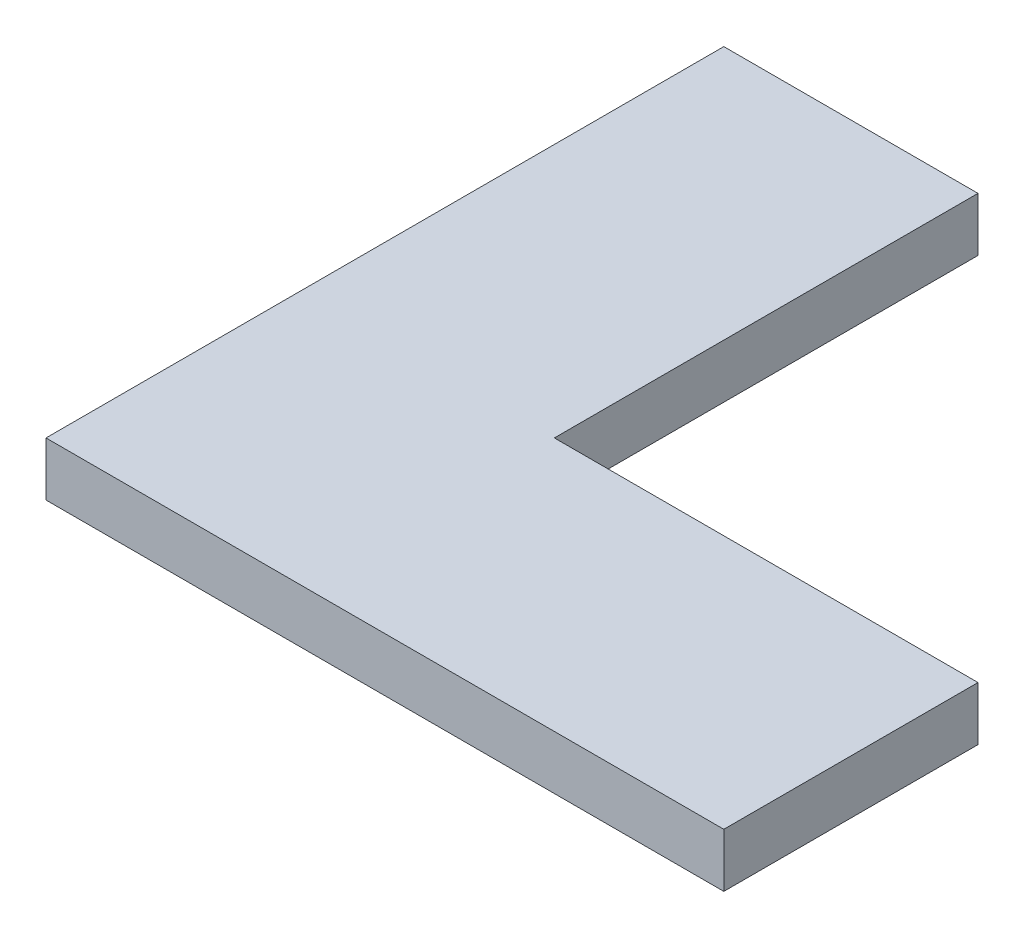
SolidWorks part; units mm, degrees
ref_plane "Front Plane" through (0, 0, 0) normal (0, 0, 1) x (1, 0, 0)
ref_plane "Top Plane" through (0, 0, 0) normal (0, 1, 0) x (1, 0, 0)
ref_plane "Right Plane" through (0, 0, 0) normal (1, 0, 0) x (0, 0, -1)
sketch "Sketch1" plane through (0, 0, 0) normal (0, 1, 0) x (1, 0, 0)
  line L0 (-40, 40) -> (-40, -40)
  line L1 (-40, -40) -> (40, -40)
  line L2 (40, -40) -> (40, -10)
  line L3 (40, -10) -> (-10, -10)
  line L4 (-10, -10) -> (-10, 40)
  line L5 (-10, 40) -> (-40, 40)
  point P5 (-40, 0)
  point P8 (0, -40)
  dimension "D1" = 50
  dimension "D2" = 30
extrude "Boss-Extrude1" add sketch "Sketch1" along normal mid plane 6.35
